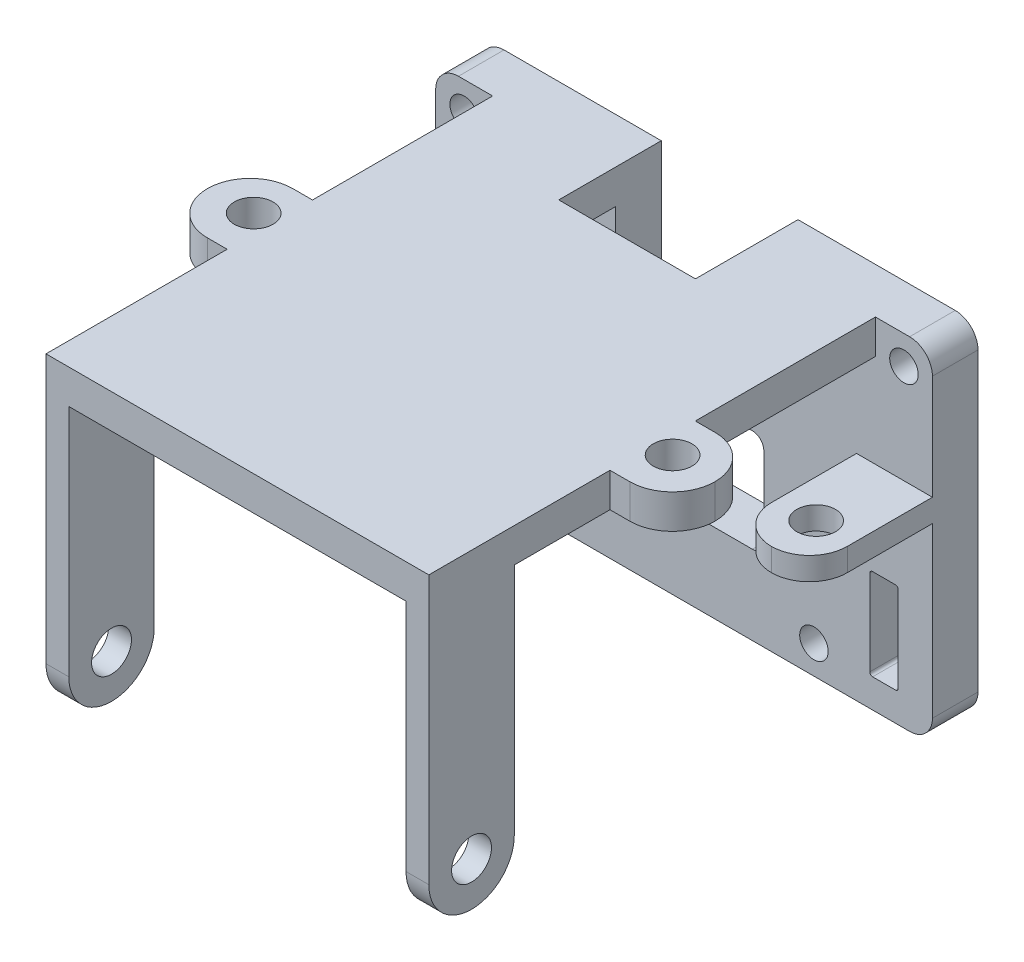
SolidWorks part; units mm, degrees
ref_plane "Front Plane" through (0, 0, 0) normal (0, 0, 1) x (1, 0, 0)
ref_plane "Top Plane" through (0, 0, 0) normal (0, 1, 0) x (1, 0, 0)
ref_plane "Right Plane" through (0, 0, 0) normal (1, 0, 0) x (0, 0, -1)
sketch "Sketch1" plane through (0, 0, 0) normal (0, 0, 1) x (1, 0, 0)
  line L1 (-16.8, -15) -> (16.8, -15)
  line L2 (-16.8, -15) -> (-16.8, 15)
  line L3 (-16.8, 15) -> (16.8, 15)
  line L4 (16.8, -15) -> (16.8, 15)
  line L5 (-16.8, -15) -> (16.8, 15) construction
  line L6 (-16.8, 15) -> (16.8, -15) construction
  point P0 (0, 0)
  dimension "D1" = 33.6
  dimension "D2" = 30
extrude "Boss-Extrude1" add sketch "Sketch1" along normal blind 4
sketch "Sketch3" plane through (0, 0, 4) normal (0, 0, 1) x (1, 0, 0)
  line L0 (16.8, -15) -> (16.8, 15) construction
  line L1 (-16.8, 15) -> (16.8, 15)
  line L2 (-16.8, 15) -> (-16.8, 12)
  line L3 (-16.8, 12) -> (16.8, 12)
  line L4 (16.8, 15) -> (16.8, 12)
  dimension "D1" = 3
extrude "Boss-Extrude2" add sketch "Sketch3" along normal blind 39.2
sketch "Sketch5" plane through (0, 0, 4) normal (0, 0, 1) x (1, 0, 0)
  line L1 (-7, -8.05) -> (7, -8.05)
  line L2 (-7, -8.05) -> (-7, 0.95)
  line L3 (-7, 0.95) -> (7, 0.95)
  line L4 (7, -8.05) -> (7, 0.95)
  line L5 (-7, -8.05) -> (7, 0.95) construction
  line L6 (-7, 0.95) -> (7, -8.05) construction
  point P0 (0, -3.55)
  dimension "D1" = 14
  dimension "D2" = 9
extrude "Cut-Extrude2" cut sketch "Sketch5" against normal blind 30
sketch "Sketch8" plane through (0, 0, 4) normal (0, 0, 1) x (1, 0, 0)
  line L1 (6, 12) -> (-6, 12)
  line L2 (6, 12) -> (6, 5)
  line L3 (6, 5) -> (-6, 5)
  line L4 (-6, 12) -> (-6, 5)
  line L5 (6, 12) -> (-6, 5) construction
  line L6 (-6, 12) -> (6, 5) construction
  point P6 (0, 8.5)
  dimension "D1" = 7
  dimension "D2" = 12
extrude "Cut-Extrude4" cut sketch "Sketch8" against normal through all
sketch "Sketch10" plane through (0, 12, 0) normal (0, -1, 0) x (1, 0, 0)
  line L0 (16.8, 43.2) -> (16.8, 4) construction
  line L1 (16.8, 43.2) -> (14.8, 43.2)
  line L2 (16.8, 43.2) -> (16.8, 35.7)
  line L3 (16.8, 35.7) -> (14.8, 35.7)
  line L4 (14.8, 43.2) -> (14.8, 35.7)
  line L5 (-16.8, 43.2) -> (16.8, 43.2) construction
  dimension "D1" = 2
  dimension "D3" = 7.5
extrude "Boss-Extrude3" add sketch "Sketch10" along normal blind 24.3
sketch "Sketch12" plane through (16.8, 0, 0) normal (1, 0, 0) x (0, 0, -1)
  line L0 (-4, -15) -> (-4, 12) construction
  line L1 (-4, 15) -> (0, 15)
  line L2 (-4, 15) -> (-4, -15)
  line L3 (-4, -15) -> (0, -15)
  line L4 (0, 15) -> (0, -15)
  line L5 (0, -15) -> (0, 15) construction
  dimension "D1" = 30
extrude "Boss-Extrude4" add sketch "Sketch12" along normal blind 5
sketch "Sketch13" plane through (0, 0, 4) normal (0, 0, 1) x (1, 0, 0)
  line L0 (18.8, -12.475) -> (16.3, -12.475)
  line L1 (18.8, -12.475) -> (18.8, -4.475)
  line L2 (16.3, -12.475) -> (16.3, -4.475)
  line L3 (18.8, -4.475) -> (16.3, -4.475)
  line L4 (18.8, -12.475) -> (16.3, -4.475) construction
  line L5 (16.3, -12.475) -> (18.8, -4.475) construction
  line L6 (-16.8, -15) -> (21.8, -15) construction
  line L7 (21.8, 15) -> (21.8, -15) construction
  dimension "D1" = 2.5
  dimension "D2" = 8
  dimension "D3" = 2.525
  dimension "D4" = 3
extrude "Cut-Extrude5" cut sketch "Sketch13" against normal through all
fillet "Fillet3" radius 0.25 4 edges at (16.3, -12.475, 2) (18.8, -12.475, 2) (18.8, -4.475, 2) (16.3, -4.475, 2)
fillet "Fillet4" radius 1 6 edges at (7, -8.05, 2) (-7, -8.05, 2) (-7, 0.95, 2) (7, 0.95, 2) (-6, 5, 2) (6, 5, 2)
sketch "Sketch15" plane through (16.8, 0, 0) normal (1, 0, 0) x (0, 0, -1)
  line L0 (-43.2, -12.3) -> (-43.2, 12) construction
  line L1 (-35.7, -12.3) -> (-43.2, -12.3) construction
  circle A1 centre (-39.45, -8.475) radius 1.75
  dimension "D1" = 3.825
  dimension "D2" = 3.75
extrude "Cut-Extrude6" cut sketch "Sketch15" against normal up to next
ref_plane "Plane1" through (0, 0, 0) normal (-1, 0, 0) x (0, 0, 1)
fillet "Fillet6" radius 3.75 2 edges at (15.8, -12.3, 35.7) (15.8, -12.3, 43.2)
sketch "Sketch23" plane through (0, 0, 4) normal (0, 0, 1) x (1, 0, 0)
  line L1 (21.8, 15) -> (21.8, -15) construction
  line L2 (21.8, 15) -> (16.8, 15) construction
  circle A0 centre (11.4, -12.5) radius 1.25
  circle A1 centre (19.3, 12.5) radius 1.25
  dimension "D3" = 2.5
  dimension "D4" = 2.5
  dimension "D5" = 2.5
extrude "Cut-Extrude8" cut sketch "Sketch23" against normal up to next
fillet "Fillet8" radius 2 2 edges at (21.8, 15, 2) (21.8, -15, 2)
sketch "Sketch24" plane through (0, 15, 0) normal (0, 1, 0) x (1, 0, 0)
  line L1 (-6, -9) -> (6, -9)
  line L2 (-6, -9) -> (-6, 9)
  line L3 (-6, 9) -> (6, 9)
  line L4 (6, -9) -> (6, 9)
  line L5 (-6, -9) -> (6, 9) construction
  line L6 (-6, 9) -> (6, -9) construction
  point P0 (0, 0)
  dimension "D1" = 12
  dimension "D2" = 18
extrude "Cut-Extrude9" cut sketch "Sketch24" against normal up to next
sketch "Esboço1" plane through (16.8, 0, 0) normal (1, 0, 0) x (0, 0, -1)
  line L0 (-43.2, 15) -> (-4, 15) construction
  line L1 (-27.3, 15) -> (-19.81, 15)
  line L2 (-27.3, 15) -> (-27.3, 12)
  line L3 (-27.3, 12) -> (-19.81, 12)
  line L4 (-19.81, 15) -> (-19.81, 12)
  line L5 (-35.7, 12) -> (-4, 12) construction
  line L6 (-4, 15) -> (-4, 12) construction
  dimension "D1" = 15.81
  dimension "D2" = 7.49
extrude "Ressalto-extrusão1" add sketch "Esboço1" along normal blind 5.475
fillet "Filete1" radius 3.7338 1 edges at (22.275, 13.5, 27.3)
fillet "Filete2" radius 3.7338 1 edges at (22.275, 13.5, 19.81)
sketch "Esboço2" plane through (0, 15, 0) normal (0, 1, 0) x (1, 0, 0)
  circle A0 centre (18.385, -23.39) radius 1.7
  dimension "D1" = 3.4
  dimension "D2" = 3.89
  dimension "D3" = 3.91
extrude "Corte-extrusão1" cut sketch "Esboço2" against normal blind 5
sketch "Esboço3" plane through (0, 0, 4) normal (0, 0, 1) x (1, 0, 0)
  line L0 (21.8, 13) -> (21.8, -13) construction
  line L1 (21.8, 3.8) -> (15.14, 3.8)
  line L2 (21.8, 3.8) -> (21.8, 1.8)
  line L3 (21.8, 1.8) -> (15.14, 1.8)
  line L4 (15.14, 3.8) -> (15.14, 1.8)
  dimension "D1" = 8.2
  dimension "D2" = 0
  dimension "D3" = 2
  dimension "D4" = 6.66
extrude "Ressalto-extrusão2" add sketch "Esboço3" along normal blind 10.8
sketch "Esboço5" plane through (0, 3.8, 0) normal (0, 1, 0) x (1, 0, 0)
  line L0 (15.14, -14.8) -> (21.8, -14.8) construction
  line L1 (21.8, -14.8) -> (21.8, -4) construction
  circle A0 centre (18.47, -10.875) radius 1.7
  dimension "D2" = 3.4
  dimension "D1" = 3.925
  dimension "D3" = 3.33
extrude "Corte-extrusão2" cut sketch "Esboço5" against normal up to next
fillet "Filete3" radius 3.33 1 edges at (21.8, 2.8, 14.8)
fillet "Filete4" radius 3.33 1 edges at (15.14, 2.8, 14.8)
mirror "Espelhar5" about plane through (0, 0, 0) normal (-1, 0, 0) of "Filete3", "Corte-extrusão2", "Filete4", "Filete2", "Ressalto-extrusão1", "Filete1", "Corte-extrusão1", "Ressalto-extrusão2", "Boss-Extrude4", "Fillet8", "Cut-Extrude8", "Fillet3", "Cut-Extrude5", "Fillet6", "Boss-Extrude3", "Cut-Extrude6"
